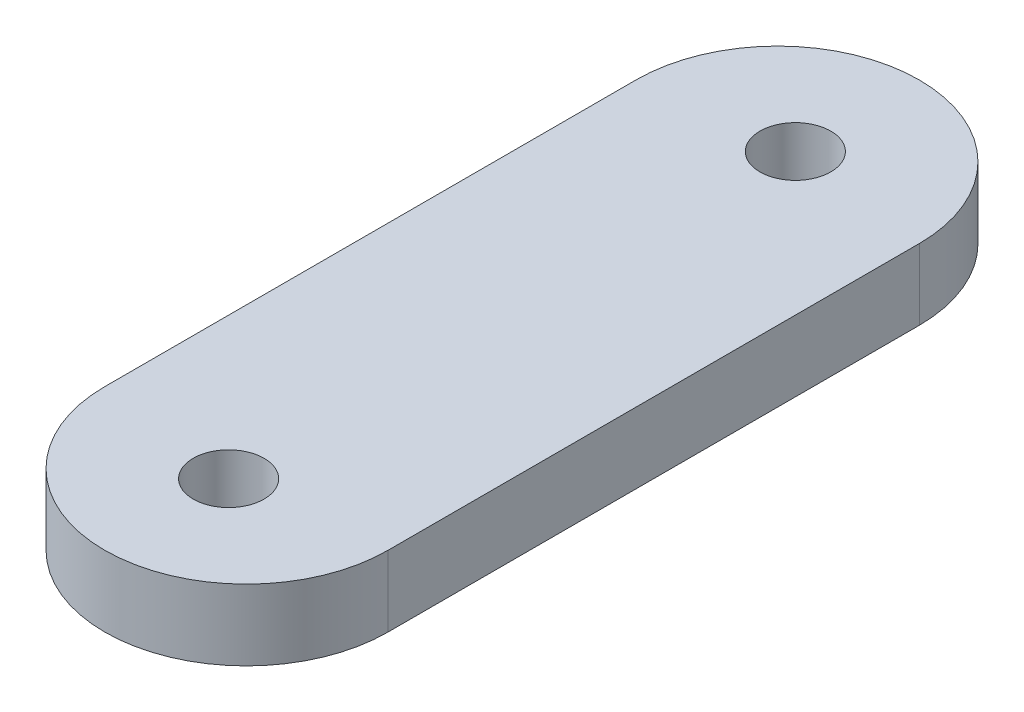
SolidWorks part; units mm, degrees
ref_plane "Front Plane" through (0, 0, 0) normal (0, 0, 1) x (1, 0, 0)
ref_plane "Top Plane" through (0, 0, 0) normal (0, 1, 0) x (1, 0, 0)
ref_plane "Right Plane" through (0, 0, 0) normal (1, 0, 0) x (0, 0, -1)
sketch "Sketch1" plane through (0, 0, 0) normal (0, 1, 0) x (1, 0, 0)
  line L0 (0, -23) -> (0, -16) construction
  line L1 (8, -23) -> (-8, -23)
  line L2 (8, -23) -> (8, 23)
  line L3 (8, 23) -> (-8, 23)
  line L4 (-8, -23) -> (-8, 23)
  line L5 (8, -23) -> (-8, 23) construction
  line L6 (8, 23) -> (-8, -23) construction
  line L7 (0, 23) -> (0, 16) construction
  circle A0 centre (0, -16) radius 2
  circle A1 centre (0, 16) radius 2
  point P0 (0, 0)
  dimension "D4" = 4
  dimension "D1" = 16
  dimension "D2" = 46
  dimension "D3" = 7
  dimension "D5" = 7
extrude "Boss-Extrude1" add sketch "Sketch1" along normal blind 4
fillet "Fillet1" 2 edges at (8, 2, 23) (-8, 2, 23) type full round first side face at (8, 2, 0) second side face at (-8, 2, 0) middle face at (0, 2, 23)
fillet "Fillet2" 2 edges at (8, 2, -23) (-8, 2, -23) type full round first side face at (8, 2, -4) second side face at (-8, 2, -4) middle face at (0, 2, -23)
